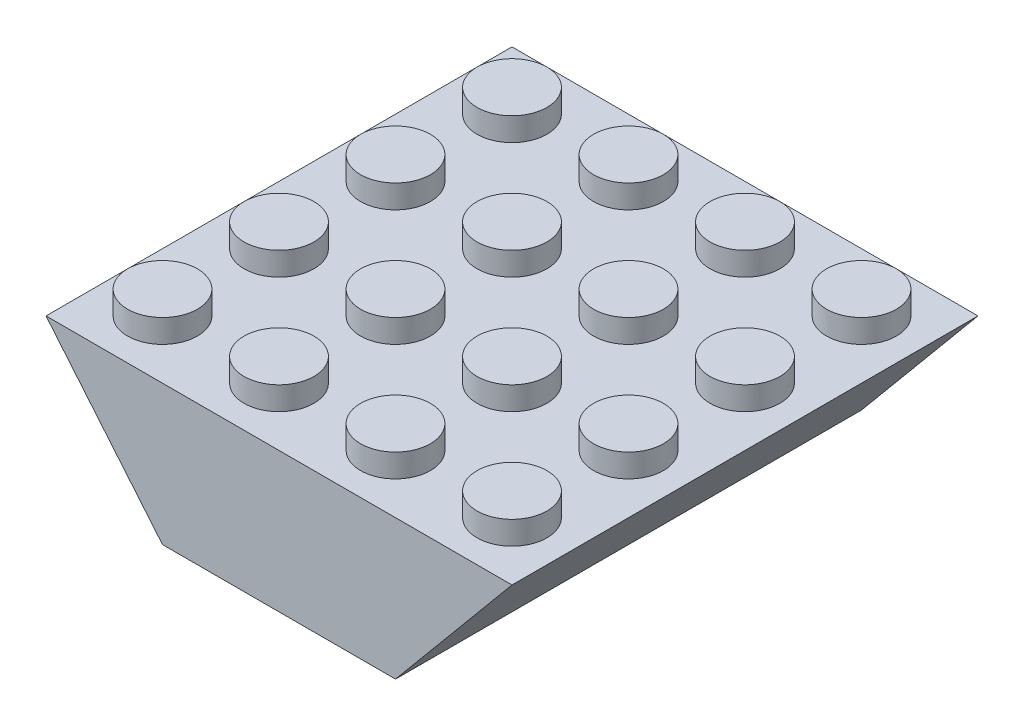
SolidWorks part; units mm, degrees
ref_plane "Front Plane" through (0, 0, 0) normal (0, 0, 1) x (1, 0, 0)
ref_plane "Top Plane" through (0, 0, 0) normal (0, 1, 0) x (1, 0, 0)
ref_plane "Right Plane" through (0, 0, 0) normal (1, 0, 0) x (0, 0, -1)
sketch "Sketch1" plane through (0, 0, 0) normal (0, 0, 1) x (1, 0, 0)
  line L0 (-8, 0) -> (8, 0)
  line L1 (8, 0) -> (16, 9.6)
  line L2 (16, 9.6) -> (-16, 9.6)
  line L3 (-16, 9.6) -> (-8, 0)
  point P4 (0, 0)
  dimension "D1" = 9.6
  dimension "D2" = 16
  dimension "D3" = 32
extrude "Boss-Extrude1" add sketch "Sketch1" along normal blind 32
sketch "Sketch2" plane through (0, 9.6, 0) normal (0, 1, 0) x (1, 0, 0)
  line L0 (-16, -32) -> (-12, -32) construction
  line L1 (16, -32) -> (-16, -32) construction
  line L2 (-12, -32) -> (-12, -28) construction
  circle A0 centre (-12, -28) radius 2.4
  dimension "D1" = 4.8
  dimension "D2" = 4
  dimension "D3" = 4
extrude "Boss-Extrude2" add sketch "Sketch2" along normal blind 1.6
pattern_linear "LPattern1" count 4 spacing 8 along (0, 0, -1) count 4 spacing 8 along (1, 0, 0) of "Boss-Extrude2"
shell "Shell1" thickness 1.6 removed face at (0, 0, 16)
